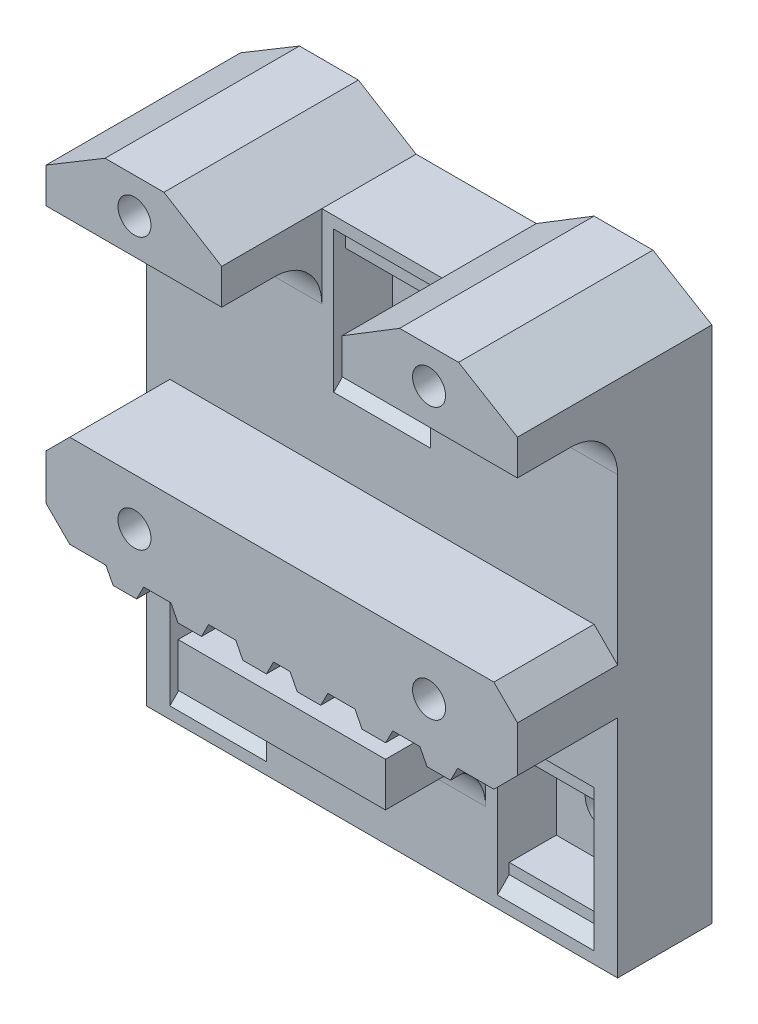
SolidWorks part; units mm, degrees
material "ABS"
ref_plane "Front Plane" through (0, 0, 0) normal (0, 0, 1) x (1, 0, 0)
ref_plane "Top Plane" through (0, 0, 0) normal (0, 1, 0) x (1, 0, 0)
ref_plane "Right Plane" through (0, 0, 0) normal (1, 0, 0) x (0, 0, -1)
sketch "Sketch1" plane through (0, 0, 0) normal (0, 0, 1) x (1, 0, 0)
  line L1 (-23.7591, 22) -> (52.715, 22) construction
  line L2 (0, -6) -> (0, 38)
  line L3 (0, 38) -> (40, 38)
  line L4 (40, -6) -> (40, 38)
  line L6 (0, -6) -> (40, -6)
  point P2 (0, 22)
  point P9 (40, 22)
  point P10 (0, 22)
  point P13 (40, 22)
  dimension "D1" = 44
  dimension "D2" = 40
extrude "Boss-Extrude1" add sketch "Sketch1" along normal blind 8
sketch "Sketch2" plane through (0, 0, 8) normal (0, 0, 1) x (1, 0, 0)
  line L0 (20, 38) -> (20, 20.7808) construction
  line L1 (15.9, 36) -> (24.1, 36)
  line L2 (15.9, 36) -> (15.9, 26)
  line L3 (15.9, 26) -> (24.1, 26)
  line L4 (24.1, 36) -> (24.1, 26)
  line L5 (40, 38) -> (0, 38) construction
  line L7 (40, 38) -> (0, 38) construction
  line L9 (2, 6) -> (10.2, 6)
  line L10 (2, 6) -> (2, -4)
  line L11 (2, -4) -> (10.2, -4)
  line L12 (10.2, 6) -> (10.2, -4)
  line L14 (29.8, 6) -> (29.8, -4)
  line L15 (38, -4) -> (29.8, -4)
  line L16 (38, 6) -> (38, -4)
  line L17 (38, 6) -> (29.8, 6)
  line L18 (15.9, 31) -> (24.1, 31) construction
  line L19 (2, 1) -> (38, 1) construction
  dimension "D1" = 8.2
  dimension "D2" = 10
  dimension "D3" = 2
  dimension "D4" = 4.1
  dimension "D5" = 30
  dimension "D6" = 2
extrude "Cut-Extrude1" cut sketch "Sketch2" against normal blind 1
sketch "Sketch3" plane through (0, 0, 7) normal (0, 0, 1) x (1, 0, 0)
  line L0 (15.9, 36) -> (15.9, 26) construction
  line L1 (15.9, 35.1) -> (24.1, 35.1)
  line L2 (15.9, 35.1) -> (15.9, 26.9)
  line L3 (15.9, 26.9) -> (24.1, 26.9)
  line L4 (24.1, 35.1) -> (24.1, 26.9)
  line L5 (24.1, 26) -> (24.1, 36) construction
  line L6 (24.1, 36) -> (15.9, 36) construction
  line L7 (15.9, 26) -> (24.1, 26) construction
  line L8 (2, 6) -> (2, -4) construction
  line L9 (2, 5.1) -> (10.2, 5.1)
  line L10 (2, 5.1) -> (2, -3.1)
  line L11 (2, -3.1) -> (10.2, -3.1)
  line L12 (10.2, 5.1) -> (10.2, -3.1)
  line L13 (10.2, -4) -> (10.2, 6) construction
  line L14 (29.8, 6) -> (29.8, -4) construction
  line L15 (29.8, 5.1) -> (38, 5.1)
  line L16 (29.8, 5.1) -> (29.8, -3.1)
  line L17 (29.8, -3.1) -> (38, -3.1)
  line L18 (38, 5.1) -> (38, -3.1)
  line L19 (38, -4) -> (38, 6) construction
  line L20 (2, -4) -> (10.2, -4) construction
  dimension "D1" = 0.9
  dimension "D2" = 0.9
  dimension "D3" = 0.9
extrude "Cut-Extrude2" cut sketch "Sketch3" against normal blind 4
chamfer "Chamfer1" distance 1 angle 45 6 edges at (20, 26, 8) (20, 36, 8) (33.9, -4, 8) (33.9, 6, 8) (6.1, -4, 8) (6.1, 6, 8)
sketch "Sketch4" plane through (0, 0, 3) normal (0, 0, 1) x (1, 0, 0)
  line L0 (24.1, 35.1) -> (15.9, 35.1) construction
  line L1 (15.9, 35.1) -> (15.9, 26.9) construction
  line L2 (2, 1) -> (38, 1) construction
  line L3 (2, 5.1) -> (2, -3.1) construction
  line L4 (38, -5) -> (38, 7) construction
  line L5 (6.1, 5.1) -> (6.1, -3.1) construction
  line L7 (2, -3.1) -> (10.2, -3.1) construction
  line L8 (33.9, 5.1) -> (33.9, -3.1) construction
  line L10 (29.8, -3.1) -> (38, -3.1) construction
  line L12 (10.2, 5.1) -> (2, 5.1) construction
  line L13 (38, 5.1) -> (29.8, 5.1) construction
  circle A0 centre (20, 31) radius 1.65
  circle A1 centre (6.1, 1) radius 1.65
  circle A2 centre (33.9, 1) radius 1.65
  dimension "D1" = 3.3
  dimension "D2" = 4.1
  dimension "D3" = 4.1
extrude "Cut-Extrude3" cut sketch "Sketch4" against normal through all
ref_plane "Plane1" through (20, 0, 0) normal (1, 0, 0) x (0, 0, -1)
sketch "Sketch5" plane through (0, 0, 8) normal (0, 0, 1) x (1, 0, 0)
  line L0 (-5.9966, 16) -> (42.103, 16) construction
  line L1 (20.7043, 11.125) -> (19.2957, 11.125)
  line L2 (28.8, 8.725) -> (28.8, 5)
  line L3 (11.2, 8.725) -> (28.8, 8.725)
  line L4 (21.3043, 9.945) -> (23.3043, 9.945)
  line L5 (20.7043, 11.125) -> (21.3043, 9.945)
  line L6 (20, -9.075) -> (20, 9.075) construction
  line L7 (20, 5) -> (20, 15.379) construction
  line L8 (-5.9966, 5) -> (42.103, 5) construction
  line L9 (26.213, 11.125) -> (24.8043, 11.125)
  line L10 (23.3043, 9.945) -> (23.9043, 11.125)
  line L11 (23.9043, 11.125) -> (24.8043, 11.125)
  line L12 (26.813, 9.945) -> (28.813, 9.945)
  line L13 (26.213, 11.125) -> (26.813, 9.945)
  line L14 (28.813, 9.945) -> (29.413, 11.125)
  line L15 (29.413, 11.125) -> (30.313, 11.125)
  line L16 (31.7217, 11.125) -> (30.313, 11.125)
  line L17 (32.3217, 9.945) -> (34.3217, 9.945)
  line L18 (31.7217, 11.125) -> (32.3217, 9.945)
  line L19 (34.3217, 9.945) -> (34.9217, 11.125)
  line L20 (34.9217, 11.125) -> (35.8217, 11.125)
  line L21 (35.8217, 11.125) -> (40, 11.125)
  line L22 (40, -6) -> (40, 38) construction
  line L23 (40, 11.125) -> (40, 19)
  line L24 (40, 19) -> (0, 19)
  line L25 (28.8, 5) -> (11.2, 5)
  line L26 (29.8, 7) -> (29.8, -5) construction
  line L27 (0, 11.125) -> (0, 19)
  line L28 (4.1783, 11.125) -> (0, 11.125)
  line L29 (5.0783, 11.125) -> (4.1783, 11.125)
  line L30 (5.6783, 9.945) -> (5.0783, 11.125)
  line L31 (8.2783, 11.125) -> (7.6783, 9.945)
  line L32 (7.6783, 9.945) -> (5.6783, 9.945)
  line L33 (8.2783, 11.125) -> (9.687, 11.125)
  line L34 (10.587, 11.125) -> (9.687, 11.125)
  line L35 (11.187, 9.945) -> (10.587, 11.125)
  line L36 (13.787, 11.125) -> (13.187, 9.945)
  line L37 (13.187, 9.945) -> (11.187, 9.945)
  line L38 (16.0957, 11.125) -> (15.1957, 11.125)
  line L39 (16.6957, 9.945) -> (16.0957, 11.125)
  line L40 (13.787, 11.125) -> (15.1957, 11.125)
  line L41 (19.2957, 11.125) -> (18.6957, 9.945)
  line L42 (18.6957, 9.945) -> (16.6957, 9.945)
  line L43 (11.2, 8.725) -> (11.2, 5)
  line L44 (-5.9966, 27) -> (42.103, 27) construction
  line L45 (-5.9966, 35) -> (42.103, 35) construction
  line L46 (0, 38) -> (0, -6) construction
  line L47 (0, 35) -> (14.9, 35)
  line L48 (0, 35) -> (0, 38)
  line L49 (5, 41) -> (10, 41)
  line L50 (14.9, 35) -> (14.9, 38)
  line L51 (0, 38) -> (5, 41)
  line L52 (14.9, 38) -> (10, 41)
  line L53 (40, 38) -> (0, 38) construction
  line L54 (25.1, 38) -> (30, 41)
  line L55 (40, 38) -> (35, 41)
  line L56 (25.1, 35) -> (25.1, 38)
  line L57 (35, 41) -> (30, 41)
  line L58 (40, 35) -> (40, 38)
  line L59 (40, 35) -> (25.1, 35)
  line L60 (15.9, 37) -> (15.9, 25) construction
  circle A0 centre (20, 31) radius 1.65 construction
  point P16 (20, 11.125)
  point P38 (20, 19)
  point P55 (20, 8.725)
  dimension "D1" = 15
  dimension "D2" = 0.6
  dimension "D3" = 0.6
  dimension "D4" = 2
  dimension "D5" = 0.9
  dimension "D7" = 4.875
  dimension "D9" = 1
  dimension "D10" = 2.4
  dimension "D11" = 3
  dimension "D14" = 5
  dimension "D15" = 1
  dimension "D16" = 5.9
  dimension "D17" = 10
  dimension "D6" = 11
  dimension "D12" = 11
  dimension "D13" = 8
  dimension "D8" = 3
extrude "Boss-Extrude2" add sketch "Sketch5" along normal blind 8.5 and the other way up to surface (8 mm away) other way up to face at (35.55, 1, 0)
fillet "Fillet1" radius 4 3 edges at (32.55, 35, 8) (7.45, 35, 8) (20, 5, 8) tangent propagation no
sketch "Sketch6" plane through (0, 0, 16.5) normal (0, 0, 1) x (1, 0, 0)
  line L0 (7.5, 41) -> (7.5, 12.6708) construction
  line L1 (10, 41) -> (5, 41) construction
  line L2 (20, 31) -> (20, 13.7163) construction
  line L3 (20, -9.075) -> (20, 9.075) construction
  circle A0 centre (7.5, 38) radius 1.4
  circle A1 centre (7.5, 15) radius 1.4
  circle A2 centre (32.5, 38) radius 1.4
  circle A3 centre (32.5, 15) radius 1.4
  dimension "D1" = 2.8
  dimension "D2" = 23
  dimension "D3" = 3
extrude "Cut-Extrude4" cut sketch "Sketch6" against normal blind 10
chamfer "Chamfer2" distance 2 angle 45 4 edges at (40, 11.125, 12.25) (0, 11.125, 12.25) (40, 19, 12.25) (0, 19, 12.25)
